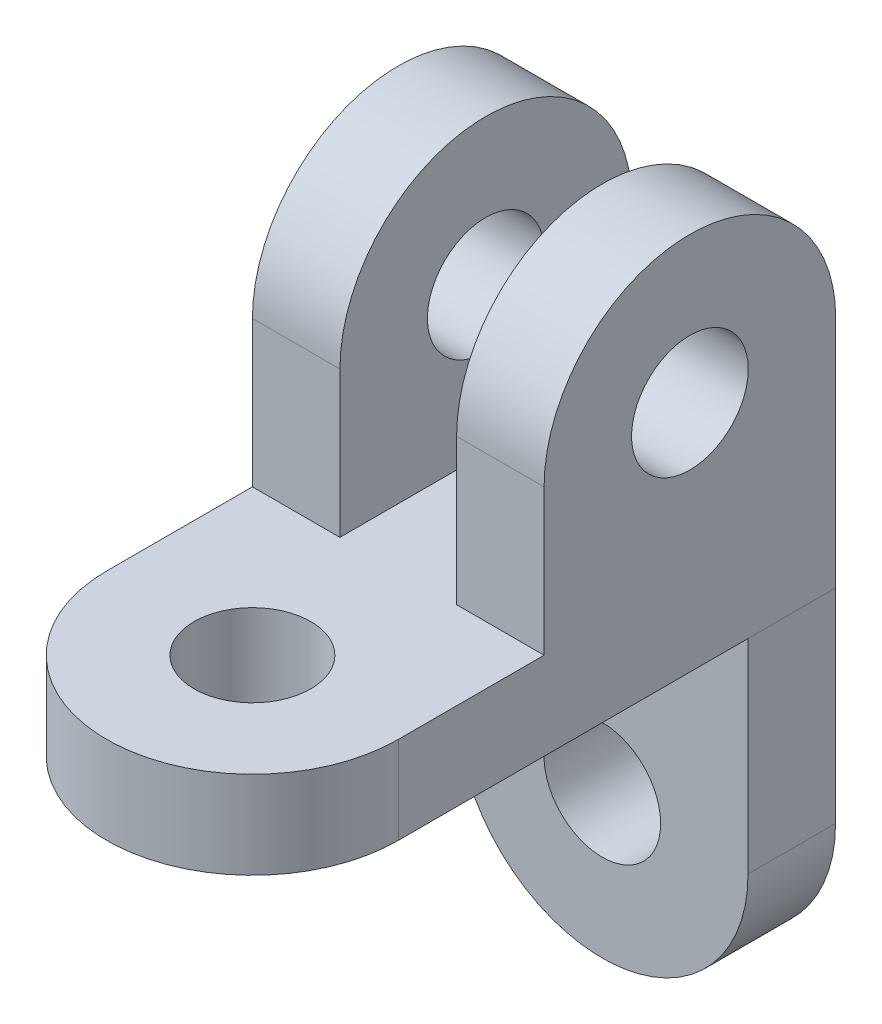
SolidWorks part; units mm, degrees
ref_plane "Front Plane" through (0, 0, 0) normal (0, 0, 1) x (1, 0, 0)
ref_plane "Top Plane" through (0, 0, 0) normal (0, 1, 0) x (1, 0, 0)
ref_plane "Right Plane" through (0, 0, 0) normal (1, 0, 0) x (0, 0, -1)
sketch "Sketch1" plane through (0, 0, 0) normal (0, 1, 0) x (1, 0, 0)
  line L0 (20, 0) -> (-20, 0)
  line L1 (-20, 0) -> (-20, -60)
  line L2 (-20, -60) -> (20, -60)
  line L3 (20, -60) -> (20, 0)
  line L4 (-20, -60) -> (20, -60)
  arc A0 (-20, -60) -> (20, -60) centre (0, -60) ccw
  circle A1 centre (0, -60) radius 8
  point P4 (0, 0)
  dimension "D3" = 16
  dimension "D1" = 60
  dimension "D2" = 40
extrude "Boss-Extrude1" add sketch "Sketch1" along normal blind 12 contours L2 L3 L0 L1 | L2 A0 region at (0, 0, 28.8369) region at (0, 0, 69.4584)
sketch "Sketch2" plane through (0, 0, 0) normal (1, 0, 0) x (0, 0, -1)
  line L0 (0, 12) -> (0, 32)
  line L1 (0, 32) -> (-40, 32)
  line L2 (-40, 32) -> (-40, 12)
  line L3 (0, 12) -> (-60, 12) construction
  line L4 (0, 12) -> (-40, 12)
  arc A0 (0, 32) -> (-40, 32) centre (-20, 32) ccw
  circle A1 centre (-20, 32) radius 8
  dimension "D3" = 16
  dimension "D1" = 20
  dimension "D2" = 40
extrude "Boss-Extrude2" add sketch "Sketch2" along normal blind 12 from offset 8 contours L4 L0 L1 L2 | L1 A0 region at (0, 21.0507, 20) region at (0, 41.4584, 20)
extrude "Boss-Extrude3" add sketch "Sketch2<3>" against normal blind 12 from offset 8 contours L1 A0 | L4 L0 L1 L2 region at (0, 21.0507, 20) region at (0, 41.4584, 20) offset against normal yes
sketch "Sketch2<3>" plane through (0, 0, 0) normal (1, 0, 0) x (0, 0, -1) same geometry as "Sketch2"
sketch "Sketch3" plane through (0, 0, 0) normal (0, 0, 1) x (1, 0, 0)
  line L0 (-20, 0) -> (-20, -28)
  line L1 (-20, -28) -> (19.9721, -28)
  line L2 (19.9721, -28) -> (20, 0)
  line L3 (20, 0) -> (-20, 0)
  arc A0 (-20, -28) -> (19.9721, -28) centre (-0.0139, -28) ccw
  circle A1 centre (-0.0139, -28) radius 8
  dimension "D2" = 16
  dimension "D1" = 28
extrude "Boss-Extrude4" add sketch "Sketch3" along normal blind 12 contours L2 L3 L0 L1 | L1 A0 region at (-0.0063, -12.9521, 0) region at (-0.0139, -37.4529, 0)
